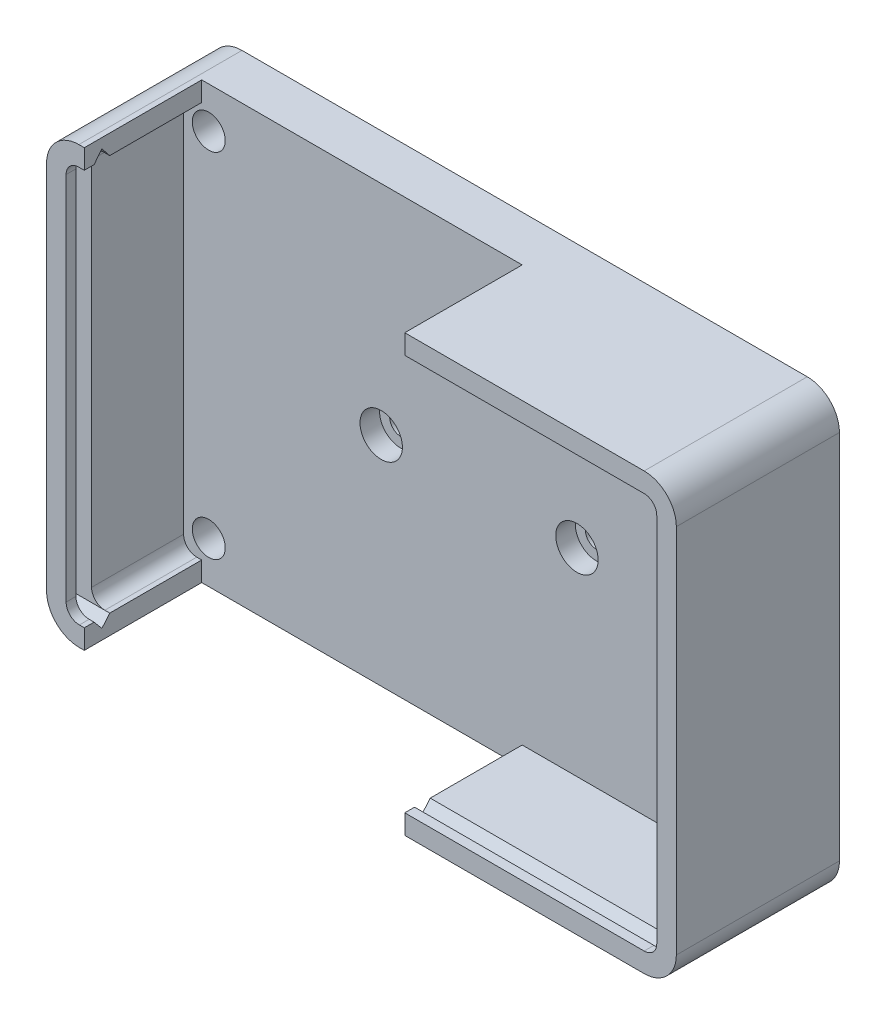
SolidWorks part; units mm, degrees
ref_plane "Front Plane" through (0, 0, 0) normal (0, 0, 1) x (1, 0, 0)
ref_plane "Top Plane" through (0, 0, 0) normal (0, 1, 0) x (1, 0, 0)
ref_plane "Right Plane" through (0, 0, 0) normal (1, 0, 0) x (0, 0, -1)
sketch "Sketch1" plane through (0, 0, -11.1517) normal (0, 0, -1) x (-1, 0, 0)
  line L0 (-25.223, 125.272) -> (-25.223, 68.523)
  line L1 (-22.223, 125.272) -> (-22.223, 68.523)
  line L2 (-113.733, 66.798) -> (-27.229, 66.798) construction
  line L26 (-27.174, 127.223) -> (-113.815, 127.223)
  line L28 (-27.174, 130.223) -> (-113.815, 130.223)
  line L29 (-118.748, 125.29) -> (-118.748, 68.431)
  line L30 (-113.815, 63.498) -> (-27.248, 63.498)
  line L39 (-115.748, 125.29) -> (-115.748, 68.431)
  line L40 (-113.815, 66.498) -> (-27.248, 66.498)
  line L42 (-22.223, 68.523) -> (-22.223, 125.272) construction
  line L43 (-25.223, 68.523) -> (-25.223, 125.272) construction
  arc A20 (-113.815, 127.223) -> (-115.748, 125.29) centre (-113.815, 125.29) ccw
  arc A21 (-113.815, 130.223) -> (-118.748, 125.29) centre (-113.815, 125.29) ccw
  arc A22 (-118.748, 68.431) -> (-113.815, 63.498) centre (-113.815, 68.431) ccw
  arc A23 (-27.248, 63.498) -> (-22.223, 68.523) centre (-27.248, 68.523) ccw
  arc A28 (-27.248, 66.498) -> (-25.223, 68.523) centre (-27.248, 68.523) ccw
  arc A29 (-25.223, 125.272) -> (-27.174, 127.223) centre (-27.174, 125.272) ccw
  arc A31 (-115.748, 68.431) -> (-113.815, 66.498) centre (-113.815, 68.431) ccw
  arc A32 (-22.223, 125.272) -> (-27.174, 130.223) centre (-27.174, 125.272) ccw
  point P3 (-21.9374, 69.0034)
  point P20 (-25.223, 68.2891)
  point P21 (0, 0)
  point P22 (0, 0)
  point P24 (0, 0)
  point P25 (-25.223, 68.4099)
  point P27 (0, 0)
  point P29 (0, 0)
  dimension "D2" = 3
  dimension "D3" = 0.3
  dimension "D1" = 0.3
  dimension "D4" = 0.3
  dimension "D5" = 0.3
extrude "Boss-Extrude1" add sketch "Sketch1" against normal blind 7
extrude "Boss-Extrude2" add sketch "Sketch1<4>" against normal blind 25
sketch "Sketch1<4>" plane through (0, 0, -11.1517) normal (0, 0, -1) x (-1, 0, 0) same geometry as "Sketch1"
sketch "Sketch2" plane through (0, 0, -4.1517) normal (0, 0, 1) x (1, 0, 0)
  circle A0 centre (111.633, 123.952) radius 2.5265
  circle A1 centre (111.633, 69.901) radius 2.5265
  circle A2 centre (29.083, 69.901) radius 2.5265
  circle A3 centre (29.083, 123.952) radius 2.5265
  dimension "D1" = 5.053
extrude "Cut-Extrude1" cut sketch "Sketch2" against normal blind 6
sketch "Sketch3" plane through (0, 0, -4.1517) normal (0, 0, 1) x (1, 0, 0)
  line L0 (70.4945, 127.223) -> (70.5315, 66.498) construction
  line L1 (27.174, 127.223) -> (113.815, 127.223) construction
  line L2 (113.815, 66.498) -> (27.248, 66.498) construction
  point P1 (85.513, 96.8605)
  point P8 (70.513, 96.8605)
  point P9 (55.513, 96.8422)
  dimension "D1" = 15
hole_wizard "CBORE for M3 SHCS1" positions "Sketch3" profile "Sketch4" counterbore size "M3" standard "ANSI Metric"
sketch "Sketch4" plane through (55.513, 96.8422, -4.1517) normal (1, 0, 0) x (0, -1, 0)
  line L0 (0, 0) -> (0, 8.0215)
  line L1 (0, 8.0215) -> (1.7, 7)
  line L2 (1.7, 7) -> (1.7, 3)
  line L3 (1.7, 3) -> (3.25, 3)
  line L4 (3.25, 3) -> (3.25, 0)
  line L5 (3.25, 0) -> (0, 0)
  line L10 (0, 8.0215) -> (-1.7, 7) construction
  line L11 (0, -6.35) -> (0, 107.95) construction
  dimension "Hole Dia." = 3.4
  dimension "Hole Depth" = 7
  dimension "C'Bore Dia." = 6.5
  dimension "C'Bore Depth" = 3
  dimension "Drill Angle" = 118
ref_plane "Plane1" through (0, 96.8605, 0) normal (0, -1, 0) x (-1, 0, 0)
sketch "Sketch5" plane through (0, 96.8605, 0) normal (0, -1, 0) x (-1, 0, 0)
  line L0 (-113.815, -13.8483) -> (-27.248, -13.8483) construction
  line L1 (-77.123, -13.8483) -> (-28.005, -13.8483)
  line L2 (-77.123, -13.8483) -> (-77.123, 4.1517)
  line L3 (-77.123, 4.1517) -> (-28.005, 4.1517)
  line L4 (-28.005, -13.8483) -> (-28.005, 4.1517)
  line L5 (-33.005, -0.3) -> (-33.005, -7.4) construction
  line L6 (-72.123, -0.3) -> (-72.123, -7.4) construction
  line L8 (-113.815, 4.1517) -> (-27.248, 4.1517) construction
  point P10 (-28.005, 4.1517)
  dimension "D1" = 5
  dimension "D2" = 5
extrude "Cut-Extrude2" cut sketch "Sketch5" against normal through all both and the other way through all
sketch "Sketch6" plane through (22.223, -0.0074, 0) normal (-1, 0, 0) x (0, 0, 1)
  line L0 (13.8483, 68.5304) -> (13.8483, 125.2794) construction
  line L1 (9.9483, 128.7304) -> (12.3483, 128.7304)
  line L2 (9.9483, 128.7304) -> (9.9483, 65.0794)
  line L3 (9.9483, 65.0794) -> (12.3483, 65.0794)
  line L4 (12.3483, 128.7304) -> (12.3483, 65.0794)
  line L6 (13.8483, 130.2304) -> (-11.1517, 130.2304) construction
  line L7 (9.9483, 127.2304) -> (11.1483, 128.7304)
  line L8 (13.8483, 127.2304) -> (-4.1517, 127.2304) construction
  line L9 (11.1483, 128.7304) -> (12.3483, 127.2304)
  line L10 (12.3483, 66.5054) -> (11.1483, 65.0794)
  line L11 (13.8483, 66.5054) -> (-4.1517, 66.5054) construction
  line L12 (11.1483, 65.0794) -> (9.9483, 66.5054)
  point P4 (13.8483, 96.9049)
  point P7 (12.3483, 96.9049)
  point P19 (0, 0)
  point P25 (0, 0)
  dimension "D1" = 1.5
  dimension "D2" = 2.4
  dimension "D3" = 1.5
extrude "Cut-Extrude3" cut sketch "Sketch6" against normal offset from surface (95.025 mm away) 1.5 contours L4 L2 | L9 L7 L2 L4 | L12 L10 L4 L2 region at (22.223, 96.8791, 11.1483) up to face at (115.748, 96.8605, 4.8483) offset beyond the face yes
